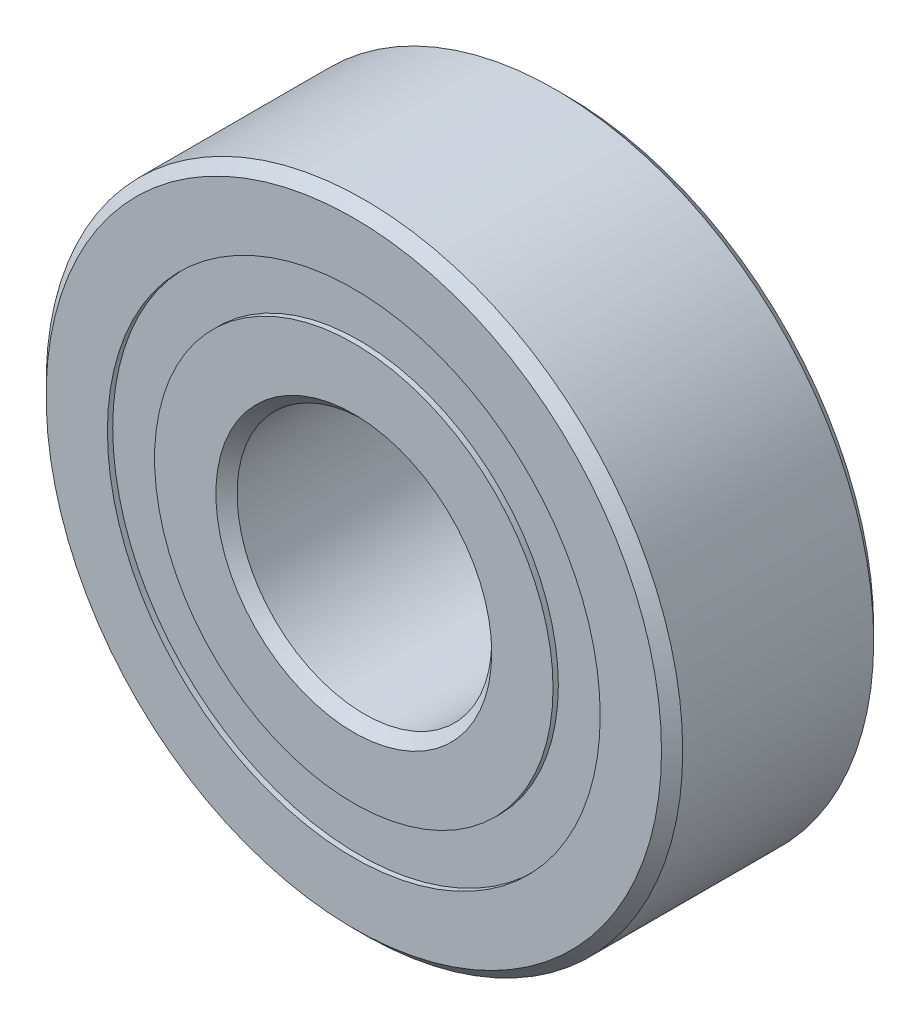
SolidWorks part; units mm, degrees
material "Chrome Stainless Steel"
ref_plane "Front Plane" through (0, 0, 0) normal (0, 0, 1) x (1, 0, 0)
ref_plane "Top Plane" through (0, 0, 0) normal (0, 1, 0) x (1, 0, 0)
ref_plane "Right Plane" through (0, 0, 0) normal (1, 0, 0) x (0, 0, -1)
sketch "Sketch1" plane through (0, 0, 0) normal (1, 0, 0) x (0, 0, -1)
  line L0 (-2.5, 0) -> (2.5, 0) construction
  line L1 (0, 7.5) -> (0, -7.5) construction
  line L2 (2.25, 7.5) -> (-2.25, 7.5)
  line L3 (-2.25, 7.5) -> (-2.5, 7.25)
  line L4 (-2.5, 7.25) -> (-2.5, 5.8056)
  line L5 (-2.5, 5.8056) -> (-1.1111, 5.8056)
  line L6 (2.5, 5.8056) -> (1.1111, 5.8056)
  line L7 (2.5, 7.25) -> (2.5, 5.8056)
  line L8 (2.25, 7.5) -> (2.5, 7.25)
  line L9 (0, 7.5) -> (0, 5.25) construction
  line L10 (0, 5.25) -> (0, 3) construction
  arc A0 (-1.1111, 5.8056) -> (1.1111, 5.8056) centre (0, 5.25) cw
  arc A1 (-1.1111, 5.8056) -> (1.1111, 5.8056) centre (0, 5.25) ccw construction
  point P14 (0, 3)
  point P15 (0, -3)
  dimension "Width" = 5
  dimension "OD" = 15
  dimension "D1" = 45
  dimension "D2" = 0.25
  dimension "D3" = 2.2222
  dimension "Shaft Dia" = 6
  dimension "D4" = 0.5556
revolve "Revolve1" add sketch "Sketch1" angle 360 about L0
sketch "Sketch2" plane through (0, 0, 0) normal (1, 0, 0) x (0, 0, -1)
  line L0 (-2.5, 4.6944) -> (-1.1111, 4.6944)
  line L1 (-2.5, 7.25) -> (-2.5, -7.25) construction
  line L2 (-2.5, 4.6944) -> (-2.5, 3.25)
  line L3 (-2.5, 3.25) -> (-2.25, 3)
  line L4 (-2.25, 3) -> (2.25, 3)
  line L5 (0, 7.5) -> (0, -7.5) construction
  line L6 (0, 3) -> (0, 4.0077) construction
  line L7 (0, 4.0077) -> (0, 3) construction
  line L8 (-2.5, 4.6944) -> (-2.5, 1.8056) construction
  line L10 (2.5, 4.6944) -> (1.1111, 4.6944)
  line L11 (2.5, 4.6944) -> (2.5, 3.25)
  line L12 (2.5, 3.25) -> (2.25, 3)
  arc A0 (-1.1111, 4.6944) -> (1.1111, 4.6944) centre (0, 5.25) ccw
  arc A1 (1.1111, 5.8056) -> (-1.1111, 5.8056) centre (0, 5.25) ccw construction
  circle A2 centre (0, 5.25) radius 1.2423 construction
  dimension "D1" = 0.25
  dimension "D2" = 45
revolve "Revolve2" add sketch "Sketch2" angle 360 about L0
sketch "Sketch3" plane through (0, 0, 0) normal (1, 0, 0) x (0, 0, -1)
  line L0 (-1.2423, 5.25) -> (1.2423, 5.25)
  line L1 (0, 5.25) -> (0, 0) construction
  circle A1 centre (0, 5.25) radius 1.2423 construction
  arc A2 (-1.2423, 5.25) -> (1.2423, 5.25) centre (0, 5.25) cw
  arc A3 (1.1111, 5.8056) -> (-1.1111, 5.8056) centre (0, 5.25) ccw construction
  dimension "D1" = 2.4845
  dimension "D2" = 5.25
revolve "Revolve3" add sketch "Sketch3" angle 360 about L0
ref_axis "Axis1" through (0, 0, -2.5) along (0, 0, 1)
pattern_circular "CirPattern1" count 12 every 30 about axis through (0, 0, -2.5) along (0, 0, 1) of bodies 104
sketch "Sketch5" plane through (0, 0, 0) normal (1, 0, 0) x (0, 0, -1)
  line L0 (-2.5, 4.6944) -> (-1.1111, 4.6944) construction
  line L1 (-2.375, 5.8056) -> (-1.2423, 5.8056)
  line L2 (-2.375, 5.8056) -> (-2.375, 4.6944)
  line L3 (-2.375, 4.6944) -> (-1.2423, 4.6944)
  line L4 (-1.2423, 5.8056) -> (-1.2423, 4.6944)
  line L5 (1.2423, 5.8056) -> (2.375, 5.8056)
  line L6 (1.2423, 5.8056) -> (1.2423, 4.6944)
  line L7 (1.2423, 4.6944) -> (2.375, 4.6944)
  line L8 (2.375, 5.8056) -> (2.375, 4.6944)
  line L9 (-2.5, 5.8056) -> (-1.1111, 5.8056) construction
  line L10 (-2.375, 7.375) -> (-2.375, 5.8056) construction
  line L11 (-2.25, 7.5) -> (-2.5, 7.25) construction
  circle A0 centre (0, 5.25) radius 1.2423 construction
revolve "Revolve5" add sketch "Sketch5" angle 360 about L0
sketch "Sketch6" plane through (0, 0, 0) normal (0, 1, 0) x (1, 0, 0)
  point P0 (7.5, -2.5)
  point P1 (7.5, 2.5)
ref_axis "Center Axis 1" through (0, 0, -3.6994) along (0, 0, 1)
ref_plane "Contact Plane 1" through (0, 0, 2.5) normal (0, 0, 1) x (1, 0, 0)
ref_plane "Contact Plane 2" through (0, 0, -2.5) normal (0, 0, -1) x (-1, 0, 0)
equation "\"D2@Sketch1\" = \"Width@Sketch1\"*.05"
equation "\"D3@Sketch1\" = \"Width@Sketch1\"/2.25"
equation "\"D4@Sketch1\" = \"D3@Sketch1\"/4"
equation "\"Balls@CirPattern1\"=\"D2@Sketch3\"*2*pi/\"D1@Sketch3\"-1"
equation "\"D2@CirPattern1\" = 360/\"Balls@CirPattern1\""
equation "\"D1@Sketch2\"=\"D2@Sketch1\""
equation "\"D1@Sketch6\"=\"Width@Sketch1\""
